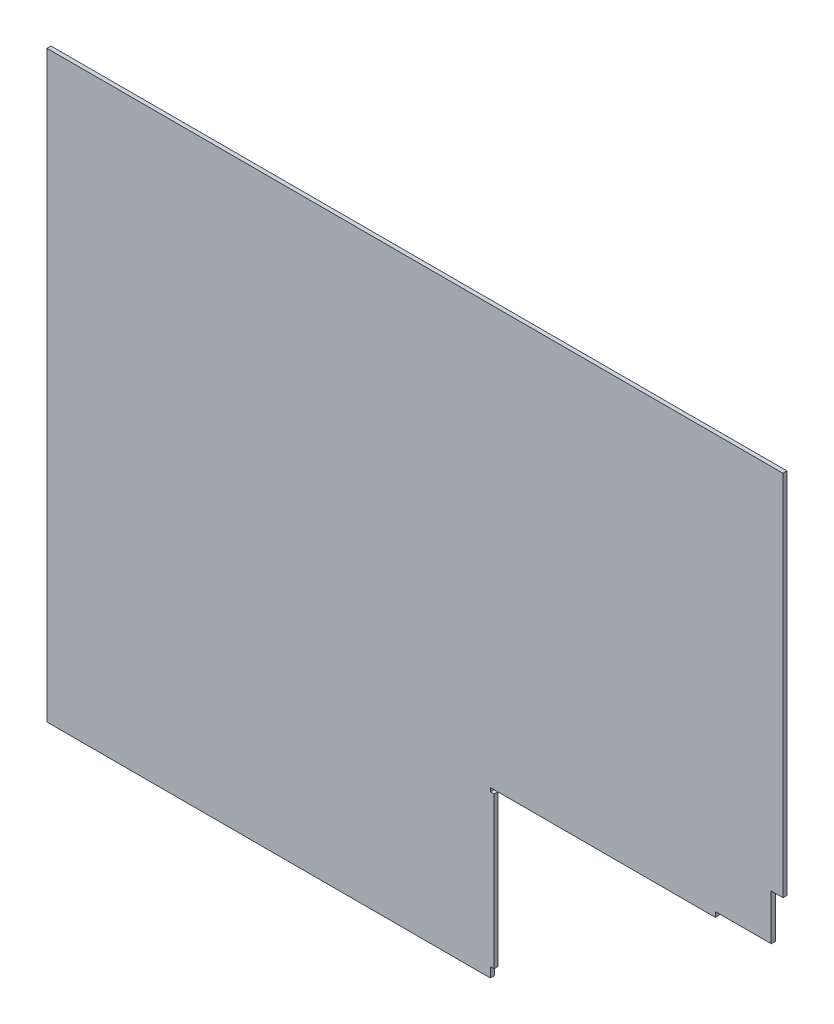
SolidWorks part; units mm, degrees
material "Acrylic (Medium-high impact)"
ref_plane "Front Plane" through (0, 0, 0) normal (0, 0, 1) x (1, 0, 0)
ref_plane "Top Plane" through (0, 0, 0) normal (0, 1, 0) x (1, 0, 0)
ref_plane "Right Plane" through (0, 0, 0) normal (1, 0, 0) x (0, 0, -1)
sketch "Sketch1" plane through (0, 0, 0) normal (0, 0, 1) x (1, 0, 0)
  line L1 (-289.5, -229.5) -> (289.5, -229.5)
  line L2 (-289.5, -229.5) -> (-289.5, 229.5)
  line L3 (-289.5, 229.5) -> (289.5, 229.5)
  line L4 (289.5, -229.5) -> (289.5, 229.5)
  line L5 (-289.5, -229.5) -> (289.5, 229.5) construction
  line L6 (-289.5, 229.5) -> (289.5, -229.5) construction
  point P0 (0, 0)
  dimension "D1" = 579
  dimension "D2" = 459
extrude "Boss-Extrude1" add sketch "Sketch1" along normal mid plane 3.175
sketch "Sketch2" plane through (0, 0, -1.5875) normal (0, 0, -1) x (-1, 0, 0)
  line L0 (-275.0972, -60.2) -> (-283.75, -60.2) construction
  line L1 (-280.75, -96.2) -> (-280.75, -61.2) construction
  line L2 (-252.237, -96.2) -> (-280.75, -96.2) construction
  line L3 (-236.75, -97.2) -> (-236.75, -99.2) construction
  line L4 (-60.75, -100.2) -> (-283.75, -100.2) construction
  line L5 (-59.75, -100.2) -> (-59.75, -102.2) construction
  line L6 (-60.75, -102.2) -> (-283.75, -102.2) construction
  line L7 (-62.75, -102.45) -> (-62.75, -221.95) construction
  line L8 (-283.75, -222.2) -> (-60.75, -222.2) construction
  line L9 (-59.75, -222.2) -> (-59.75, -224.2) construction
  line L10 (-280.75, -60.2) -> (-289.5, -60.2) construction
  line L11 (-280.75, -96.2) -> (-280.75, -60.2) construction
  line L12 (-236.75, -96.2) -> (-280.75, -96.2) construction
  line L13 (-236.75, -96.2) -> (-236.75, -100.2) construction
  line L14 (-59.75, -100.2) -> (-236.75, -100.2) construction
  line L15 (-59.75, -100.2) -> (-59.75, -102.2) construction
  line L16 (-59.75, -102.2) -> (-62.75, -102.2) construction
  line L17 (-62.75, -102.2) -> (-62.75, -222.2) construction
  line L18 (-62.75, -222.2) -> (-59.75, -222.2) construction
  line L19 (-59.75, -222.2) -> (-59.75, -229.5) construction
  line L20 (-289.5, -60.2) -> (-289.5, -229.5) construction
  line L21 (-289.5, -229.5) -> (-289.5, 229.5) construction
  line L22 (-289.5, -229.5) -> (-59.75, -229.5) construction
  line L23 (-280.25, -59.7) -> (-290, -59.7)
  line L24 (-290, -59.7) -> (-290, -230)
  line L25 (-290, -230) -> (-59.25, -230)
  line L26 (-59.25, -221.7) -> (-59.25, -230)
  line L27 (-62.25, -221.7) -> (-59.25, -221.7)
  line L28 (-62.25, -102.7) -> (-62.25, -221.7)
  line L29 (-59.25, -102.7) -> (-62.25, -102.7)
  line L30 (-59.25, -99.7) -> (-59.25, -102.7)
  line L31 (-59.25, -99.7) -> (-236.25, -99.7)
  line L32 (-236.25, -95.7) -> (-236.25, -99.7)
  line L33 (-236.25, -95.7) -> (-280.25, -95.7)
  line L34 (-280.25, -95.7) -> (-280.25, -59.7)
  dimension "D1" = 0.5
extrude "Cut-Extrude1" cut sketch "Sketch2" against normal up to surface (3.175 mm away) up to face at (0, 0, 1.5875)
